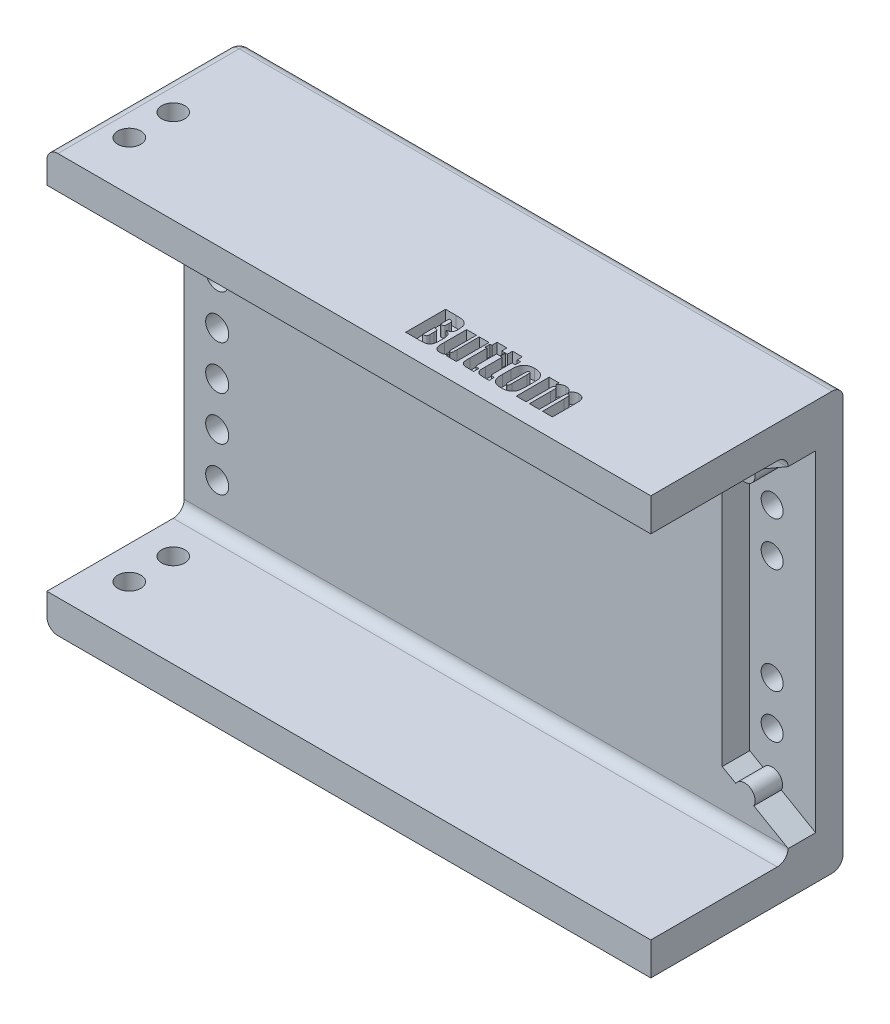
SolidWorks part; units mm, degrees
material "ABS"
ref_plane "前基準面" through (0, 0, 0) normal (0, 0, 1) x (1, 0, 0)
ref_plane "上基準面" through (0, 0, 0) normal (0, 1, 0) x (1, 0, 0)
ref_plane "右基準面" through (0, 0, 0) normal (1, 0, 0) x (0, 0, -1)
sketch "草圖2" plane through (0, 0, 0) normal (0, 0, 1) x (1, 0, 0)
  line L1 (-42.4346, 62.0442) -> (67.4854, 62.0442)
  line L2 (-42.4346, 62.0442) -> (-42.4346, -13.9558)
  line L3 (-42.4346, -13.9558) -> (67.4854, -13.9558)
  line L4 (67.4854, 62.0442) -> (67.4854, -13.9558)
  dimension "D1" = 109.92
  dimension "D2" = 76
extrude "填料-伸長1" add sketch "草圖2" along normal blind 10
sketch "草圖3" plane through (0, 0, 10) normal (0, 0, 1) x (1, 0, 0)
  line L0 (67.4854, 54.1442) -> (67.4854, -6.0558)
  line L1 (67.4854, -13.9558) -> (67.4854, 62.0442) construction
  line L2 (67.4854, 62.0442) -> (-42.4346, 62.0442) construction
  line L3 (67.4854, 54.1442) -> (55.4854, 47.2142)
  line L4 (55.4854, 47.2142) -> (55.4854, 0.8742)
  line L5 (55.4854, 0.8742) -> (67.4854, -6.0558)
  circle A0 centre (59.5654, 49.6442) radius 1.9
  circle A1 centre (59.5654, -1.5558) radius 1.9
  line M6 (67.4854, -13.9558) -> (67.4854, 62.0442)
  dimension "D7" = 7.92
  dimension "D8" = 7.92
  dimension "D9" = 3.8
  dimension "D10" = 3.8
  dimension "D12" = 12.4
  dimension "D1" = 60.2
  dimension "D2" = 7.9
  dimension "D3" = 12
  dimension "D4" = 12
  dimension "D5" = 46.34
  dimension "D6" = 6.93
  dimension "D11" = 51.2
extrude "除料-伸長1" cut sketch "草圖3" against normal blind 5 contours A1 L5 L3 A0 L4 M6 region at (61.776, 24.0442, 10)
sketch "草圖4" plane through (0, 0, 5) normal (0, 0, 1) x (1, 0, 0)
  line L0 (67.4854, -6.0558) -> (67.4854, 54.1442) construction
  circle A0 centre (59.5654, 41.6442) radius 2
  arc A1 (57.953, 48.6392) -> (61.2418, 50.5385) centre (59.5654, 49.6442) ccw construction
  circle A2 centre (59.5654, 33.6442) radius 2
  circle A3 centre (59.5654, 6.4442) radius 2
  arc A4 (61.2418, -2.4501) -> (57.953, -0.5508) centre (59.5654, -1.5558) ccw construction
  circle A5 centre (59.5654, 14.4442) radius 2
  dimension "D1" = 7.92
  dimension "D2" = 8
  dimension "D3" = 4
  dimension "D5" = 4
  dimension "D6" = 7.92
  dimension "D7" = 8
  dimension "D4" = 2
  dimension "D8" = 2
extrude "除料-伸長2" cut sketch "草圖4" against normal through all
sketch "草圖5" plane through (0, 0, 10) normal (0, 0, 1) x (1, 0, 0)
  line L0 (67.4854, -13.9558) -> (67.4854, -6.0558) construction
  line L1 (-42.4346, -13.9558) -> (67.4854, -13.9558)
  line L2 (-42.4346, -13.9558) -> (-42.4346, -7.9558)
  line L3 (-42.4346, -7.9558) -> (67.4854, -7.9558)
  line L4 (67.4854, -13.9558) -> (67.4854, -7.9558)
  line L5 (-42.4346, 62.0442) -> (-42.4346, -13.9558) construction
  line L6 (67.4854, 62.0442) -> (-42.4346, 62.0442)
  line L7 (67.4854, 62.0442) -> (67.4854, 56.0442)
  line L8 (67.4854, 56.0442) -> (-42.4346, 56.0442)
  line L9 (-42.4346, 62.0442) -> (-42.4346, 56.0442)
  dimension "D1" = 6
  dimension "D2" = 6
extrude "填料-伸長2" add sketch "草圖5" along normal blind 25
sketch "草圖7" plane through (0, -7.9558, 0) normal (0, 1, 0) x (1, 0, 0)
  line L0 (67.4854, -10) -> (-42.4346, -10) construction
  line L1 (-42.4346, -35) -> (-42.4346, -10) construction
  circle A0 centre (-36.4346, -18) radius 2.1
  circle A1 centre (-36.4346, -26) radius 2.1
  dimension "D1" = 4.2
  dimension "D2" = 8
  dimension "D4" = 6
  dimension "D3" = 2
extrude "除料-伸長3" cut sketch "草圖7" against normal through all both and the other way through all
sketch "草圖9" plane through (0, 0, 10) normal (0, 0, 1) x (1, 0, 0)
  line L2 (-42.4346, 56.0442) -> (-42.4346, -7.9558) construction
  line L3 (67.4854, -7.9558) -> (-42.4346, -7.9558) construction
  circle A0 centre (-36.4346, 0.0442) radius 2.1
  circle A1 centre (-36.4346, 8.0442) radius 2.1
  circle A2 centre (-36.4346, 16.0442) radius 2.1
  circle A3 centre (-36.4346, 24.0442) radius 2.1
  circle A4 centre (-36.4346, 32.0442) radius 2.1
  circle A5 centre (-36.4346, 40.0442) radius 2.1
  circle A6 centre (-36.4346, 48.0442) radius 2.1
  dimension "D1" = 6
  dimension "D2" = 4.2
  dimension "D3" = 8
  dimension "D4" = 7
extrude "除料-伸長4" cut sketch "草圖9" against normal through all
sketch "草圖10" plane through (0, 0, 0) normal (0, 0, -1) x (-1, 0, 0)
  line L0 (36.4346, 0.0442) -> (36.4346, 48.0442) construction
  line L1 (32.4346, 0.0442) -> (32.4346, 48.0442)
  line L2 (40.4346, 0.0442) -> (40.4346, 48.0442)
  arc A0 (32.4346, 0.0442) -> (40.4346, 0.0442) centre (36.4346, 0.0442) ccw
  arc A1 (40.4346, 48.0442) -> (32.4346, 48.0442) centre (36.4346, 48.0442) ccw
  point P4 (36.4346, 24.0442)
  dimension "D1" = 8
extrude "除料-伸長5" cut sketch "草圖10" against normal blind 5
fillet "圓角1" radius 2 7 edges at (12.5254, 56.0442, 10) (12.5254, -7.9558, 10) (-42.4346, 62.0442, 17.5) (-42.4346, -13.9558, 17.5) (-42.4346, 24.0442, 0) (12.5254, -13.9558, 0) (12.5254, 62.0442, 0)
sketch "草圖11" plane through (0, 62.0442, 62.0442) normal (0, -1, 0) x (-1, 0, 0)
  text T0 "Buttom" font "Impact" height in points 26
extrude "除料-伸長6" cut sketch "草圖11" along normal blind 2
